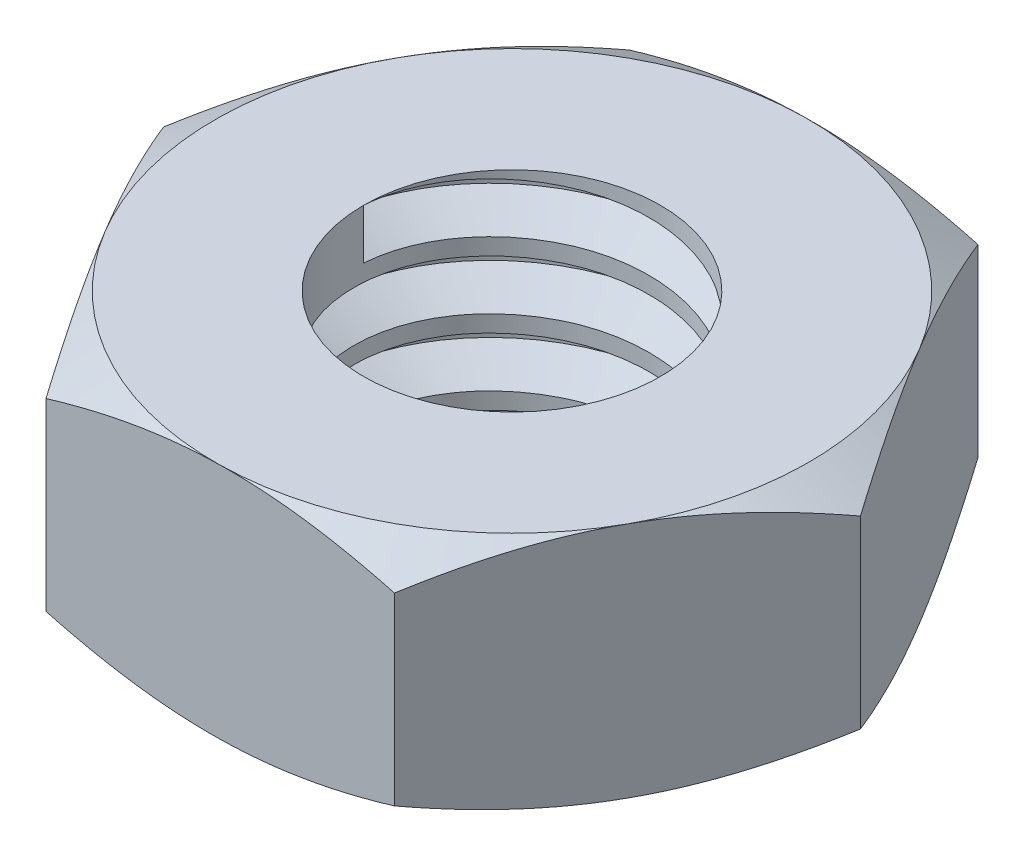
SolidWorks part; units mm, degrees
ref_plane "Front Plane" through (0, 0, 0) normal (0, 0, 1) x (1, 0, 0)
ref_plane "Top Plane" through (0, 0, 0) normal (0, 1, 0) x (1, 0, 0)
ref_plane "Right Plane" through (0, 0, 0) normal (1, 0, 0) x (0, 0, -1)
sketch "Sketch1" plane through (0, 0, 0) normal (0, 1, 0) x (1, 0, 0)
  line L1 (1.1882, -1.9803) -> (2.3091, 0.0388)
  line L2 (2.3091, 0.0388) -> (1.1209, 2.0191)
  line L3 (1.1209, 2.0191) -> (-1.1882, 1.9803)
  line L4 (-1.1882, 1.9803) -> (-2.3091, -0.0388)
  line L5 (-2.3091, -0.0388) -> (-1.1209, -2.0191)
  line L6 (-1.1209, -2.0191) -> (1.1882, -1.9803)
  circle A0 centre (0, 0) radius 2 construction
  dimension "D1" = 4
extrude "Boss-Extrude1" add sketch "Sketch1" along normal blind 1.6
sketch "Sketch2" plane through (0, 1.6, 0) normal (0, 1, 0) x (1, 0, 0)
  circle A0 centre (0, 0) radius 1
  dimension "D1" = 2
extrude "Cut-Extrude1" cut sketch "Sketch2" against normal through all
sketch "Sketch3" plane through (0, 1.6, 0) normal (0, 1, 0) x (1, 0, 0)
  line L0 (2.3091, 0.0388) -> (1.1209, 2.0191) construction
  circle A0 centre (0, 0) radius 2
extrude "Cut-Extrude2" cut sketch "Sketch3" against normal blind 1.6 draft 60 flip side to cut
sketch "Sketch4" plane through (0, 0, 0) normal (0, -1, 0) x (1, 0, 0)
  line L0 (1.1882, 1.9803) -> (2.3091, -0.0388) construction
  circle A0 centre (0, 0) radius 2
extrude "Cut-Extrude3" cut sketch "Sketch4" against normal blind 1.6 draft 60 flip side to cut
thread "Thread1" pitch 0.45 method cut profile "Thread Profile1" start angle 0, offset 0, length 2, pitch 0.45, diameter 2
ref_plane "Plane1" through (-1, 1.6, 0) normal (0, 0, 1) x (-1, 0, 0)
sketch "Thread Profile1" plane through (-1, 1.6, 0) normal (0, 0, 1) x (-1, 0, 0)
  line L0 (0, 0) -> (0, 0.45) construction
  line L1 (0, 0) -> (0.2436, 0.1406)
  line L2 (0.2436, 0.1406) -> (0.2436, 0.1969)
  line L3 (0.2436, 0.1969) -> (0, 0.3375)
  line L4 (0.2436, 0.1687) -> (0, 0.1687) construction
  line L11 (0, 0) -> (0, 0.3375)
  point P2 (0, 0)
  dimension "Pitch" = 0.45
  dimension "Profile_Angle" = 60
  dimension "Profile_Land" = 0.0562
  dimension "Profile_Height" = 0.2436
